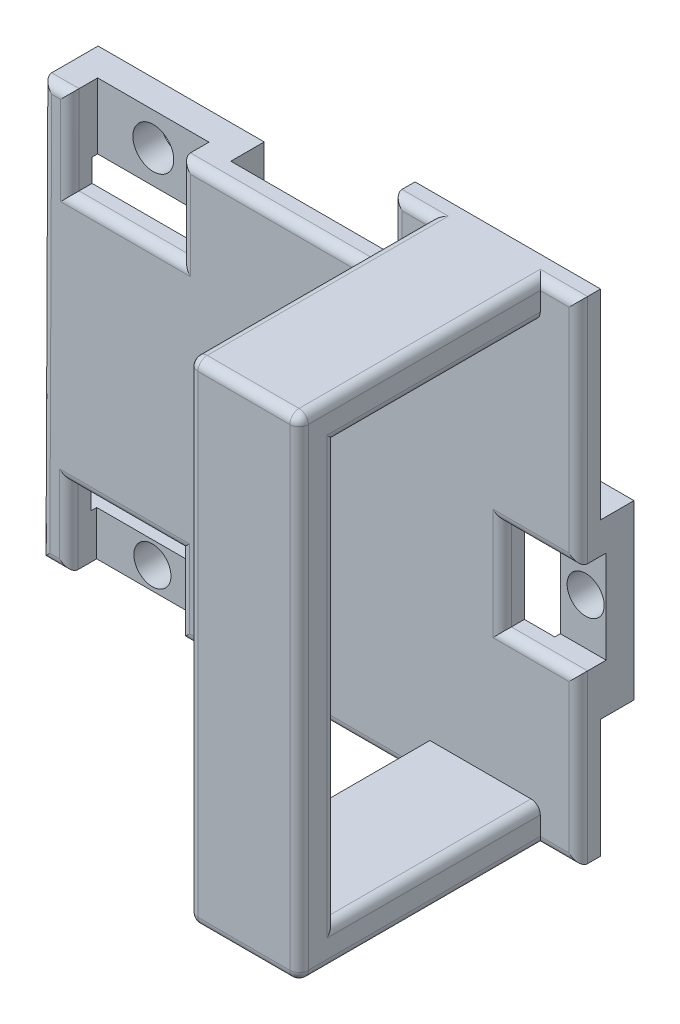
SolidWorks part; units mm, degrees
ref_plane "Płaszczyzna przednia" through (0, 0, 0) normal (0, 0, 1) x (1, 0, 0)
ref_plane "Płaszczyzna górna" through (0, 0, 0) normal (0, 1, 0) x (1, 0, 0)
ref_plane "Płaszczyzna prawa" through (0, 0, 0) normal (1, 0, 0) x (0, 0, -1)
sketch "Szkic1" plane through (0, 0, 158.8329) normal (0, 0, 1) x (1, 0, 0)
  line L0 (-31.9233, -22.4743) -> (2.0767, -22.4743) construction
  line L1 (-19.5, -20.0743) -> (-10.4467, -20.0743)
  line L2 (-19.5, -20.0743) -> (-19.5, -22.4743)
  line L3 (-19.5, -22.4743) -> (-10.4467, -22.4743)
  line L4 (-10.4467, -20.0743) -> (-10.4467, -22.4743)
  line L5 (-19.5, -20.0743) -> (-10.4467, -22.4743) construction
  line L6 (-19.5, -22.4743) -> (-10.4467, -20.0743) construction
  line L12 (9.4816, -6.7768) -> (7.0127, -6.7768)
  line L13 (9.4816, -6.7768) -> (9.4816, -16.0838)
  line L14 (-19.4004, -3.549) -> (-10.4467, -3.549)
  line L15 (-19.4004, -3.549) -> (-19.4004, 0)
  line L16 (-19.4004, 0) -> (-10.4467, 0)
  line L17 (-10.4467, -3.549) -> (-10.4467, 0)
  line L18 (-19.4004, -3.549) -> (-10.4467, 0) construction
  line L19 (-19.4004, 0) -> (-10.4467, -3.549) construction
  line L20 (9.4816, -16.0838) -> (7.0127, -16.0838)
  line L21 (7.0127, -6.7768) -> (7.0127, -16.0838)
  circle A0 centre (8.3767, -10.9743) radius 1 construction
  circle A1 centre (-14.9733, -21.2743) radius 1 construction
  circle A2 centre (-14.9235, -1.7745) radius 1.1 construction
  circle A3 centre (8.3767, -10.9743) radius 1
  circle A4 centre (-14.9733, -21.2743) radius 1
  circle A5 centre (-14.9235, -1.7745) radius 1.1
extrude "Dodanie-wyciągnięcie1" add sketch "Szkic1" along normal blind 1.8
sketch "Szkic2" plane through (0, 0, 160.6329) normal (0, 0, 1) x (1, 0, 0)
  line L0 (9.4816, -16.0838) -> (9.4816, -6.7768) construction
  line L1 (9.4816, 0) -> (-19.4004, 0)
  line L2 (9.4816, 0) -> (9.4816, -22.4743)
  line L3 (9.4816, -22.4743) -> (-19.5, -22.4743)
  line L4 (-19.4004, 0) -> (-19.5, -22.4743)
  circle A0 centre (8.3767, -10.9743) radius 1 construction
  circle A1 centre (-14.9733, -21.2743) radius 1 construction
  circle A2 centre (-14.9235, -1.7745) radius 1.1 construction
  circle A3 centre (8.3767, -10.9743) radius 1
  circle A4 centre (-14.9733, -21.2743) radius 1
  circle A5 centre (-14.9235, -1.7745) radius 1.1
  point P5 (0, 0)
  point P7 (0, 0)
extrude "Dodanie-wyciągnięcie2" add sketch "Szkic2" along normal blind 1.2
sketch "Szkic3" plane through (0, 0, 161.8329) normal (0, 0, 1) x (1, 0, 0)
  line L1 (-19.4893, -20.0743) -> (-19.5, -20.0743) construction
  line L3 (-17.9235, -4.7745) -> (-11.9235, -4.7745)
  line L4 (-19.4893, -20.0743) -> (-19.5, -20.0743)
  line L5 (5.3767, -8.4743) -> (5.3767, -13.4743)
  line L7 (-11.9733, -18.2743) -> (-17.9733, -18.2743)
  line L8 (9.4816, 0) -> (-19.4004, 0) construction
  line L9 (-17.9235, -4.7745) -> (-11.9235, -4.7745)
  line L10 (-17.9235, -4.7745) -> (-17.9235, 0)
  line L11 (-17.9235, 0) -> (-11.9235, 0)
  line L12 (-11.9235, -4.7745) -> (-11.9235, 0)
  line L13 (9.4816, -22.4743) -> (9.4816, 0) construction
  line L14 (5.3767, -8.4743) -> (9.4816, -8.4743)
  line L15 (5.3767, -8.4743) -> (5.3767, -13.4743)
  line L16 (5.3767, -13.4743) -> (9.4816, -13.4743)
  line L17 (9.4816, -8.4743) -> (9.4816, -13.4743)
  line L18 (-19.5, -22.4743) -> (9.4816, -22.4743) construction
  line L19 (-17.9733, -18.2743) -> (-11.9733, -18.2743)
  line L20 (-17.9733, -18.2743) -> (-17.9733, -22.4743)
  line L21 (-17.9733, -22.4743) -> (-11.9733, -22.4743)
  line L22 (-11.9733, -18.2743) -> (-11.9733, -22.4743)
  circle A0 centre (-14.9235, -1.7745) radius 1.1 construction
  circle A1 centre (8.3767, -10.9743) radius 1 construction
  circle A2 centre (-14.9733, -21.2743) radius 1 construction
  circle A3 centre (-14.9235, -1.7745) radius 1.1
  circle A4 centre (8.3767, -10.9743) radius 1
  circle A5 centre (-14.9733, -21.2743) radius 1
  point P36 (-15.0345, -21.2641)
  line M11 (9.4816, -22.4743) -> (9.4816, 0)
  line M12 (9.4816, 0) -> (-19.4004, 0)
  line M14 (-19.5, -22.4743) -> (9.4816, -22.4743)
  circle M15 centre (8.3767, -10.9743) radius 1
  circle M16 centre (-14.9733, -21.2743) radius 1
  circle M17 centre (-14.9235, -1.7745) radius 1.1
  dimension "D1" = 3
  dimension "D2" = 3
  dimension "D3" = 2.5
  dimension "D4" = 2.5
  dimension "D5" = 3
  dimension "D6" = 3
  dimension "D7" = 3
  dimension "D8" = 3
  dimension "D9" = 3
extrude "Wytnij-wyciągnięcie1" cut sketch "Szkic3" against normal blind 1.5 contours L5 L16 L14 M11 M15 | L3 L12 L10 M12 M17 | L22 L7 L20 M14 M16 region at (-17.8469, -2.3872, 161.8329) region at (-14.9733, -20.2461, 161.8329) region at (7.2579, -10.9743, 161.8329)
sketch "Szkic7" plane through (0, 0, 0) normal (0, 1, 0) x (1, 0, 0)
  line L0 (9.4816, -160.6329) -> (-10.4467, -160.6329) construction
  line L1 (9.4816, -161.8329) -> (-0.5184, -161.8329)
  line L2 (9.4816, -161.8329) -> (9.4816, -160.6329)
  line L3 (9.4816, -160.6329) -> (-0.5184, -160.6329)
  line L4 (-0.5184, -161.8329) -> (-0.5184, -160.6329)
  dimension "D1" = 10
extrude "Dodanie-wyciągnięcie3" add sketch "Szkic7" along normal blind 4
sketch "Szkic8" plane through (0, 0, 161.8329) normal (0, 0, 1) x (1, 0, 0)
  line L0 (-0.5184, 4) -> (9.4816, 4) construction
  line L1 (7.432, 4) -> (1.4816, 4)
  line L2 (7.432, 4) -> (7.432, 2)
  line L3 (7.432, 2) -> (1.4816, 2)
  line L4 (1.4816, 4) -> (1.4816, 2)
  line L6 (-11.9733, -22.4743) -> (9.4816, -22.4743) construction
  line L7 (7.432, -22.4743) -> (1.4816, -22.4743)
  line L8 (7.432, -22.4743) -> (7.432, -20.4743)
  line L9 (7.432, -20.4743) -> (1.4816, -20.4743)
  line L10 (1.4816, -22.4743) -> (1.4816, -20.4743)
  line L11 (9.4816, -22.4743) -> (9.4816, -13.4743) construction
  line L12 (9.4816, -8.4743) -> (9.4816, 4) construction
  point P14 (0, 0)
  dimension "D1" = 2
  dimension "D2" = 8
  dimension "D3" = 8
extrude "Dodanie-wyciągnięcie4" add sketch "Szkic8" along normal blind 11
sketch "Szkic9" plane through (0, 0, 172.8329) normal (0, 0, 1) x (1, 0, 0)
  line L1 (7.432, 4) -> (1.4816, 4)
  line L2 (7.432, 4) -> (7.432, -22.4743)
  line L3 (7.432, -22.4743) -> (1.4816, -22.4743)
  line L4 (1.4816, 4) -> (1.4816, -22.4743)
extrude "Dodanie-wyciągnięcie5" add sketch "Szkic9" along normal blind 2
fillet "Zaokrąglenie4" radius 0.5 33 edges at (0.4816, 4, 161.8329) (-0.5184, 2, 161.8329) (-6.221, 0, 161.8329) (-11.9235, -2.3872, 161.8329) (-14.9235, -4.7745, 161.8329) (-17.9235, -2.3872, 161.8329) (-18.662, 0, 161.8329) (-19.4502, -11.2371, 161.8329) (-18.7366, -22.4743, 161.8329) (-17.9733, -20.3743, 161.8329) (-14.9733, -18.2743, 161.8329) (-11.9733, -20.3743, 161.8329) (-5.2459, -22.4743, 161.8329) (8.4568, 4, 161.8329) (9.4816, -2.2371, 161.8329) (7.4291, -8.4743, 161.8329) (5.3767, -10.9743, 161.8329) (7.4291, -13.4743, 161.8329) (9.4816, -17.9743, 161.8329) (8.4568, -22.4743, 161.8329) (7.432, 4, 168.3329) (7.432, 2, 167.3329) (7.432, -9.2371, 172.8329) (7.432, -20.4743, 167.3329) (7.432, -9.2371, 174.8329) (4.4568, 4, 174.8329) (1.4816, -9.2371, 174.8329) (1.4816, -9.2371, 172.8329) (1.4816, 4, 168.3329) (1.4816, 2, 167.3329) (1.4816, -22.4743, 168.3329) (4.4568, -22.4743, 174.8329) (7.432, -22.4743, 168.3329)
